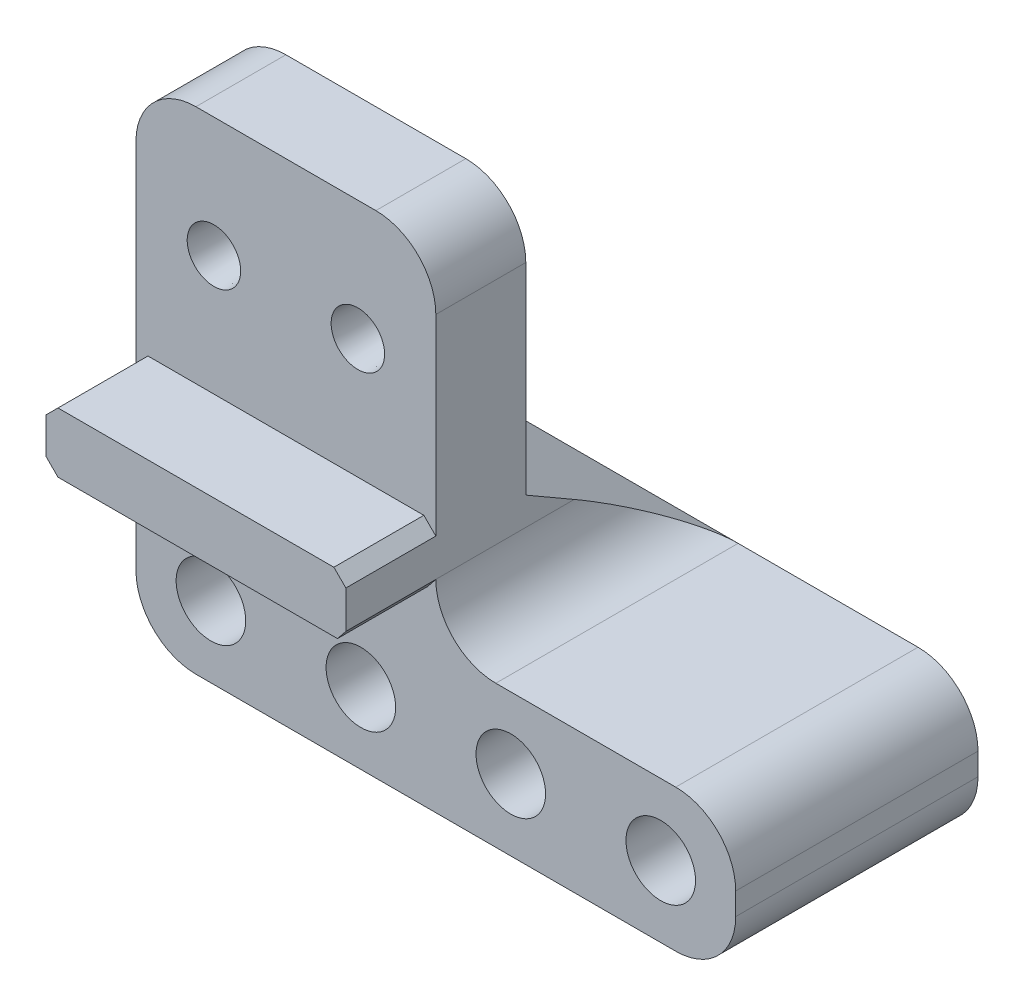
SolidWorks part; units mm, degrees
ref_plane "Front Plane" through (0, 0, 0) normal (0, 0, 1) x (1, 0, 0)
ref_plane "Top Plane" through (0, 0, 0) normal (0, 1, 0) x (1, 0, 0)
ref_plane "Right Plane" through (0, 0, 0) normal (1, 0, 0) x (0, 0, -1)
sketch "Sketch4" plane through (0, 0, 5) normal (0, 0, -1) x (-1, 0, 0)
  line L1 (31.635, 0.2) -> (-18.365, 0.2)
  line L2 (31.635, 0.2) -> (31.635, -39.8)
  line L3 (31.635, -39.8) -> (-18.365, -39.8)
  line L4 (-18.365, 0.2) -> (-18.365, -39.8)
  line L7 (-55.865, 0.2) -> (89.2881, 0.2) construction
  line L8 (102.3066, -39.8) -> (-55.865, -39.8) construction
  dimension "D1" = 50
  dimension "D2" = 70
extrude "Boss-Extrude2" add sketch "Sketch4" along normal blind 15
hole_wizard "O (0.316) Diameter Hole1" positions "Sketch7" profile "Sketch9" hole size "O" standard "ANSI Inch" end condition through all
sketch "Sketch7" plane through (0, 0, 5) normal (0, 0, 1) x (1, 0, 0)
  line L0 (-31.635, -19.8) -> (-18.635, -19.8) construction
  line L1 (-31.635, -39.8) -> (-31.635, 0.2) construction
  line L3 (5.365, -19.8) -> (18.365, -19.8) construction
  line L4 (18.365, 0.2) -> (18.365, -39.8) construction
  line L6 (-18.635, -19.8) -> (5.365, -19.8) construction
  arc A0 (58.165, -23.1782) -> (58.165, -16.4218) centre (58.165, -19.8) ccw construction
  arc A1 (58.165, -23.1782) -> (58.165, -16.4218) centre (58.165, -19.8) ccw
  point P0 (-18.635, -19.8)
  point P2 (5.365, -19.8)
  dimension "D1" = 13
sketch "Sketch9" plane through (-18.635, -19.8, 5) normal (1, 0, 0) x (0, -1, 0)
  line L0 (0, 0) -> (0, 15)
  line L1 (0, 15) -> (4.0132, 15)
  line L2 (4.0132, 15) -> (4.0132, 6.35)
  line L3 (4.0132, 6.35) -> (4.4572, 0)
  line L5 (4.4572, 0) -> (0, 0)
  line L6 (-4.0132, 6.35) -> (-4.4572, 0) construction
  line L11 (0, -6.35) -> (0, 107.95) construction
  dimension "Thru Hole Dia." = 8.0264
  dimension "Thru Hole Depth" = 15
  dimension "Near C'Sink Dia." = 8.9145
  dimension "Near C'Sink Angle" = 8
sketch "Sketch10" plane through (0, 0, -10) normal (0, 0, -1) x (-1, 0, 0)
  line L0 (31.635, -39.8) -> (31.635, 0.2) construction
  line L1 (-18.365, -39.8) -> (31.635, -39.8)
  line L2 (-18.365, -39.8) -> (-18.365, -81.75)
  line L3 (-18.365, -81.75) -> (31.635, -81.75)
  line L4 (31.635, -39.8) -> (31.635, -81.75)
  line L5 (-18.365, -39.8) -> (31.635, -39.8) construction
  line L6 (-18.365, 0.2) -> (-18.365, -39.8) construction
  arc A0 (105.9347, 0.2) -> (97.3353, 0.2) centre (101.635, -11.75) ccw construction
  arc A1 (105.9347, 0.2) -> (97.3353, 0.2) centre (101.635, -11.75) ccw
  line M7 (-18.365, -39.8) -> (31.635, -39.8)
  dimension "D1" = 70
extrude "Boss-Extrude3" add sketch "Sketch10" against normal up to surface (15 mm away) contours L4 L2 L3 M7 region at (-6.635, -60.775, -10) up to face at (-14.1778, -19.8, 5)
sketch "Sketch12" plane through (0, 0, 5) normal (0, 0, 1) x (1, 0, 0)
  line L0 (-31.635, -81.75) -> (-31.635, 0.2) construction
  line L1 (-31.635, -49.8) -> (18.365, -49.8)
  line L2 (-31.635, -49.8) -> (-31.635, -39.8)
  line L3 (-31.635, -39.8) -> (18.365, -39.8)
  line L4 (18.365, -49.8) -> (18.365, -39.8)
  line L5 (18.365, 0.2) -> (18.365, -81.75) construction
  line L6 (-102.3066, -39.8) -> (55.865, -39.8) construction
  dimension "D1" = 10
extrude "Boss-Extrude5" add sketch "Sketch12" along normal blind 15
sketch "Sketch11" plane through (0, 0, -10) normal (0, 0, -1) x (-1, 0, 0)
  line L0 (31.635, -81.75) -> (31.635, 0.2) construction
  line L1 (31.635, -58.05) -> (-68.365, -58.05)
  line L2 (31.635, -58.05) -> (31.635, -81.75)
  line L3 (-18.365, -81.75) -> (-68.365, -81.75)
  line L4 (-68.365, -58.05) -> (-68.365, -81.75)
  line L5 (-5.365, -81.75) -> (-5.365, -58.05) construction
  line L6 (-18.365, 0.2) -> (-18.365, -81.75) construction
  line L7 (31.635, -81.75) -> (-18.365, -81.75)
  line L8 (-18.365, -81.75) -> (31.635, -81.75) construction
  line L9 (-18.365, -81.75) -> (31.635, -81.75)
  line L10 (31.635, -81.75) -> (31.635, -49.8)
  line L11 (31.635, -49.8) -> (-18.365, -49.8)
  line L12 (-18.365, -81.75) -> (-18.365, -49.8)
  point P9 (-5.365, -69.9)
  point P16 (0, 0)
  line M9 (31.635, -81.75) -> (31.635, 0.2)
  line M11 (-18.365, 0.2) -> (-18.365, -81.75)
  line M12 (-18.365, -81.75) -> (31.635, -81.75)
  dimension "D2" = 23.7
  dimension "100mm" = 100
extrude "Boss-Extrude4" add sketch "Sketch11" against normal up to surface (15 mm away) and the other way blind 25.4 contours L5 L1 M12 M11 | L5 L9 L1 M9 | L1 L4 L3 M11 region at (-13.135, -69.9, -10) region at (11.865, -69.9, -10) region at (43.365, -69.9, -10) up to face at (-6.635, -19.8, 5)
sketch "Sketch14" plane through (0, 0, -35.4) normal (0, 0, -1) x (-1, 0, 0)
  line L0 (-68.365, -69.9) -> (-55.865, -69.9) construction
  line L1 (-68.365, -58.05) -> (-68.365, -81.75) construction
  line L2 (-55.865, -69.9) -> (-30.865, -69.9) construction
  line L3 (-30.865, -69.9) -> (-5.865, -69.9) construction
  line L4 (-5.865, -69.9) -> (19.135, -69.9) construction
  line L5 (19.135, -69.9) -> (31.635, -69.9) construction
  line L6 (31.635, -81.75) -> (31.635, -58.05) construction
  point P10 (0, 0)
  point P11 (0, 0)
  point P12 (0, 0)
  point P13 (0, 0)
  dimension "D1" = 25
  dimension "D2" = 12.5
hole_wizard "O (0.316) Diameter Hole2" positions "Sketch17" profile "Sketch19" hole size "O" standard "ANSI Inch" end condition through all
sketch "Sketch17" plane through (0, 0, -35.4) normal (0, 0, -1) x (-1, 0, 0)
  point P0 (-55.865, -69.9)
  point P3 (-30.865, -69.9)
  point P6 (-5.865, -69.9)
  point P9 (19.135, -69.9)
sketch "Sketch19" plane through (55.865, -69.9, -35.4) normal (1, 0, 0) x (0, 1, 0)
  line L0 (0, 0) -> (0, 55.4)
  line L1 (0, 55.4) -> (4.0132, 55.4)
  line L2 (4.0132, 55.4) -> (4.0132, 6.3499)
  line L3 (4.0132, 6.3499) -> (4.4572, 0)
  line L5 (4.4572, 0) -> (0, 0)
  line L6 (-4.0132, 6.3499) -> (-4.4572, 0) construction
  line L11 (0, -6.35) -> (0, 107.95) construction
  dimension "Thru Hole Dia." = 8.0264
  dimension "Thru Hole Depth" = 55.4
  dimension "Near C'Sink Dia." = 8.9145
  dimension "Near C'Sink Angle" = 8
sketch "Sketch13" plane through (0, 0, 5) normal (0, 0, 1) x (1, 0, 0)
  line L6 (18.365, -49.8) -> (-31.635, -49.8)
  line L7 (-31.635, -49.8) -> (-31.635, -81.75)
  line L8 (-31.635, -81.75) -> (68.365, -81.75)
  line L9 (68.365, -81.75) -> (68.365, -58.05)
  line L10 (68.365, -58.05) -> (18.365, -58.05)
  line L11 (18.365, -58.05) -> (18.365, -49.8)
  line L12 (18.365, -49.8) -> (-31.635, -49.8)
  line L13 (-31.635, -49.8) -> (-31.635, -81.75)
  line L14 (-31.635, -81.75) -> (68.365, -81.75)
  line L15 (68.365, -81.75) -> (68.365, -58.05)
  line L16 (68.365, -58.05) -> (18.365, -58.05)
  line L17 (18.365, -58.05) -> (18.365, -49.8)
  circle A0 centre (-19.135, -69.9) radius 5.8
  circle A1 centre (5.865, -69.9) radius 5.8
  circle A2 centre (30.865, -69.9) radius 5.8
  circle A3 centre (55.865, -69.9) radius 5.8
  circle A4 centre (30.865, -69.9) radius 4.0132 construction
  circle A6 centre (-19.135, -69.9) radius 4.0132 construction
  circle A7 centre (5.865, -69.9) radius 4.0132 construction
  circle A9 centre (55.865, -69.9) radius 4.0132 construction
  point P14 (0, 0)
  point P17 (0, 0)
  point P22 (0, 0)
  point P25 (0, 0)
  point P28 (0, 0)
  circle M25 centre (55.865, -69.9) radius 4.0132
  circle M26 centre (30.865, -69.9) radius 4.0132
  circle M27 centre (5.865, -69.9) radius 4.0132
  circle M28 centre (-19.135, -69.9) radius 4.0132
  dimension "D2" = 11.6
  dimension "D1" = 0
extrude "Cut-Extrude1" cut sketch "Sketch13" against normal offset from surface (25.4 mm away) 15 contours A0 M28 | A1 M27 | A2 M26 | A3 M25 region at (-24.771, -69.9, 5) region at (0.229, -69.9, 5) region at (25.229, -69.9, 5) region at (50.229, -69.9, 5) up to face at (51.4077, -69.9, -35.4)
chamfer "Chamfer3" distance 25.4 angle 30 1 edges at (-6.635, -58.05, -10) first distance on face at (18.365, -58.05, -13.4667)
fillet "Fillet1" radius 10 6 edges at (-31.635, -81.75, -15.2) (68.365, -58.05, -15.2) (68.365, -81.75, -15.2) (18.365, 0.2, -2.5) (-31.635, 0.2, -2.5) (18.365, -58.05, -15.2)
chamfer "Chamfer2" distance 2 angle 45 4 edges at (18.365, -39.8, 12.5) (-31.635, -39.8, 12.5) (-31.635, -49.8, 12.5) (18.5193, -49.8, 12.5) first distance on face at (18.365, -34.0979, 1.7029) first distance on face at (-6.635, -39.8, 12.5) first distance on face at (-31.635, -44.3735, -3.08) first distance on face at (21.1482, -52.6107, -1.1778)
